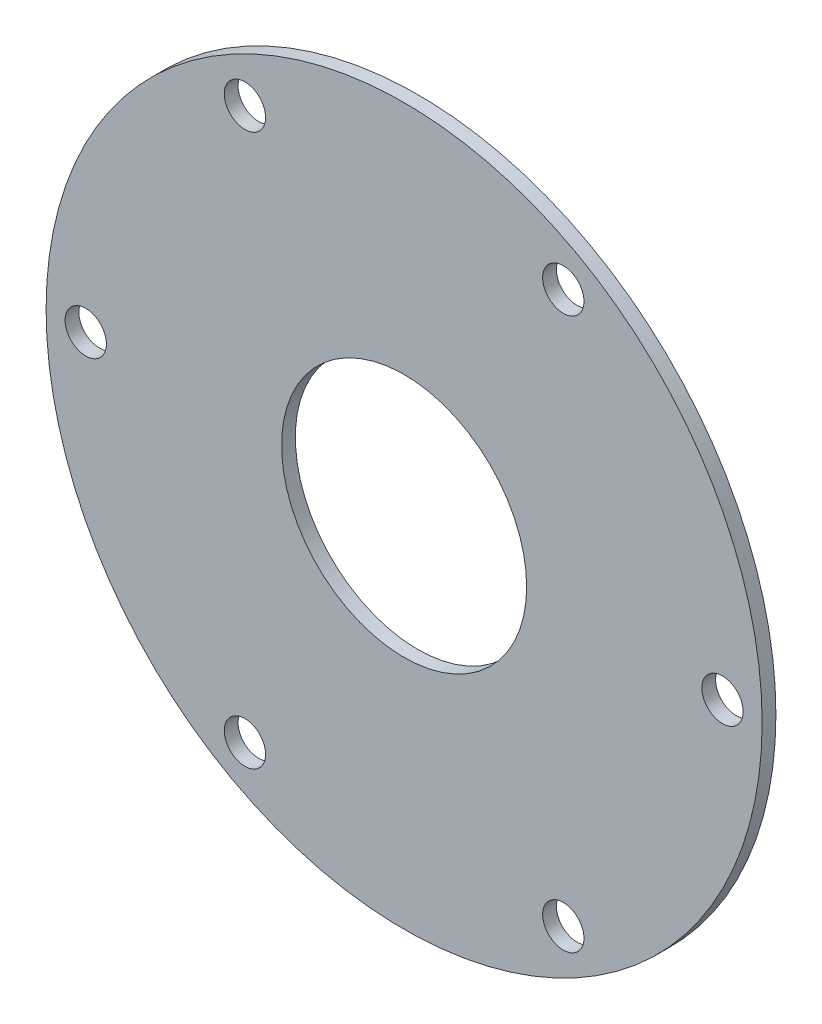
SolidWorks part; units mm, degrees
material "Resina de melamina"
ref_plane "Alzado" through (0, 0, 0) normal (0, 0, 1) x (1, 0, 0)
ref_plane "Planta" through (0, 0, 0) normal (0, 1, 0) x (1, 0, 0)
ref_plane "Vista lateral" through (0, 0, 0) normal (1, 0, 0) x (0, 0, -1)
sketch "Croquis1" plane through (0, 0, 0) normal (0, 0, 1) x (1, 0, 0)
  line L0 (0, 0) -> (-23.12, 0) construction
  circle A0 centre (0, 0) radius 26
  circle A1 centre (-23.12, 0) radius 1.5
  circle A2 centre (0, 0) radius 26
  circle A3 centre (-11.56, 20.0225) radius 1.5
  circle A4 centre (0, 0) radius 26
  circle A5 centre (11.56, 20.0225) radius 1.5
  circle A6 centre (0, 0) radius 26
  circle A7 centre (23.12, 0) radius 1.5
  circle A8 centre (0, 0) radius 26
  circle A9 centre (11.56, -20.0225) radius 1.5
  circle A10 centre (0, 0) radius 26
  circle A11 centre (-11.56, -20.0225) radius 1.5
  circle A12 centre (0, 0) radius 8.9
  dimension "D2" = 3
  dimension "D4" = 52
  dimension "D5" = 17.8
  dimension "D1" = 23.12
  dimension "D3" = 6
extrude "Saliente-Extruir1" add sketch "Croquis1" along normal blind 1 contours A0 A12 A1 A11 A9 A7 A5 A3 region at (-25.2646, 0, 0)
